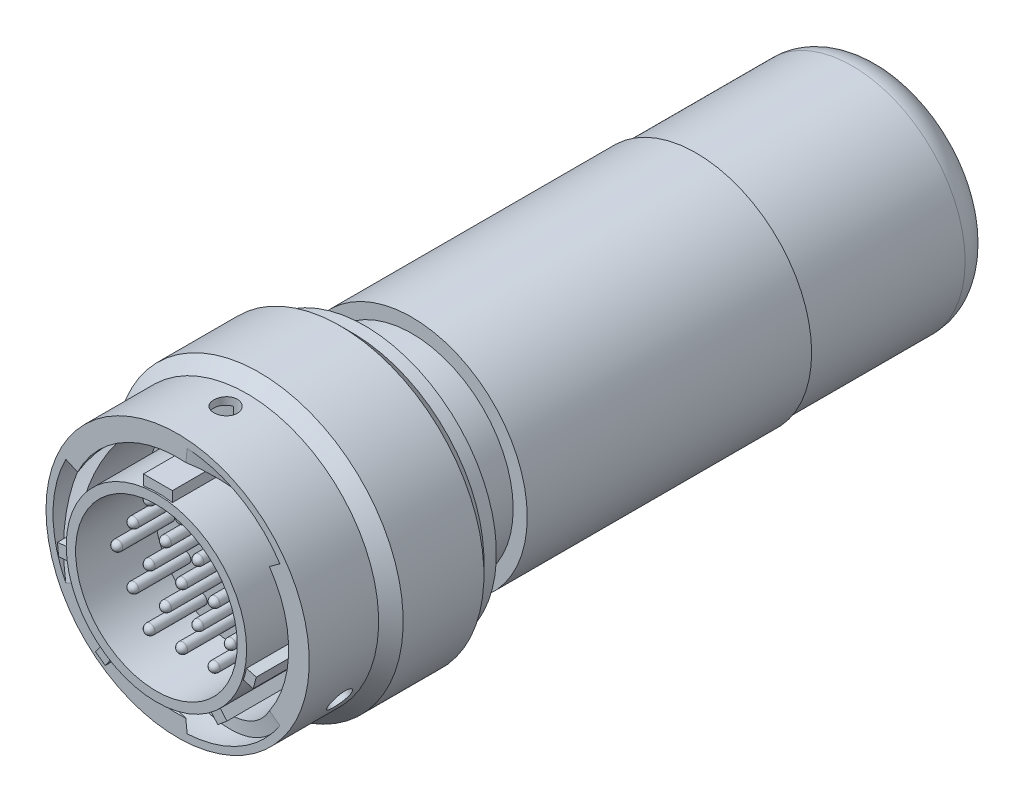
SolidWorks part; units mm, degrees
ref_plane "Front Plane" through (0, 0, 0) normal (0, 0, 1) x (1, 0, 0)
ref_plane "Top Plane" through (0, 0, 0) normal (0, 1, 0) x (1, 0, 0)
ref_plane "Right Plane" through (0, 0, 0) normal (1, 0, 0) x (0, 0, -1)
sketch "Sketch1" plane through (0, 0, 0) normal (1, 0, 0) x (0, 0, -1)
  line L0 (0, 0) -> (74, 0) construction
  line L1 (0, 14.65) -> (0, -14.65) construction
  line L2 (26, 11.75) -> (26, -11.75) construction
  line L3 (74, 11.5) -> (74, -11.5) construction
  line L4 (0, 11.303) -> (0, -11.303) construction
  line L6 (0, 8.2296) -> (0, -8.2296) construction
  line L7 (0, 9.1821) -> (0, -9.1821) construction
  line L8 (7.9502, 8.1407) -> (7.9502, -8.1407) construction
  line L10 (0, 13.4) -> (0, -13.4) construction
  line L13 (0, 0) -> (7.9502, 0) construction
  line L14 (32.5, 10.3187) -> (32.5, -10.3187) construction
  line L15 (9.2202, 10.2235) -> (9.2202, -10.2235) construction
  line L16 (0, 12.7) -> (0, -12.7) construction
  line L17 (32.5, 10.3187) -> (31.23, 10.3187) construction
  point P12 (0.1524, 0)
  point P14 (7.9502, 0)
  point P21 (2.159, 0)
  point P22 (5.842, 0)
  point P25 (30.722, 0)
  point P29 (26, 0)
  point P30 (23.356, 0)
  point P34 (32.5, 0)
  point P42 (9.2202, 0)
  dimension "D1" = 7.366
sketch "Sketch2" plane through (0, 0, 0) normal (0, 0, 1) x (1, 0, 0)
  circle A0 centre (0, 0) radius 9.1821 construction
  circle A1 centre (0, 0) radius 10.2235 construction
  circle A2 centre (0, 0) radius 14.65 construction
  circle A3 centre (0, 0) radius 12.7 construction
sketch "Sketch3" plane through (0, 0, 0) normal (1, 0, 0) x (0, 0, -1)
  line L0 (0, 0) -> (74, 0) construction
  line L1 (9.7282, 10.2235) -> (9.7282, 9.0488)
  line L2 (0, 9.1821) -> (9.2202, 9.1821)
  line L3 (0, 9.1821) -> (0, 8.2296)
  line L4 (0, 8.2296) -> (32.5, 8.2296)
  line L5 (19.8, 9.0488) -> (21.07, 10.3187)
  line L6 (9.7282, 9.0488) -> (19.8, 9.0488)
  line L7 (7.9502, 8.1407) -> (30.722, 8.1407)
  line L8 (7.9502, 8.1407) -> (7.9502, 0)
  line L9 (7.9502, 0) -> (30.722, 0)
  line L10 (30.722, 8.1407) -> (30.722, 0)
  line L11 (21.07, 10.3187) -> (31.23, 10.3187)
  line L12 (31.23, 10.3187) -> (32.5, 9.0488)
  line L13 (31.23, 10.3187) -> (32.5, 10.3187) construction
  line L14 (32.5, 10.3187) -> (32.5, 9.0488) construction
  line L15 (19.8, 9.0488) -> (19.8, 10.3187) construction
  line L16 (19.8, 10.3187) -> (21.07, 10.3187) construction
  line L26 (32.5, 9.0488) -> (32.5, 8.2296)
  line L31 (9.7282, 10.2235) -> (9.2202, 10.2235)
  line L35 (9.2202, 10.2235) -> (9.2202, 9.1821)
  dimension "D1" = 12.7
  dimension "D2" = 0.508
revolve "Revolve1" add sketch "Sketch3" angle 360 about L0
sketch "Sketch4" plane through (0, 0, 0) normal (0, 0, 1) x (1, 0, 0)
  line L0 (-1.4732, 10.1168) -> (1.4732, 10.1168)
  line L1 (0, 10.1168) -> (0, 0) construction
  line L2 (0, 0) -> (9.8576, -2.6413) construction
  line L3 (0, 0) -> (6.5598, -7.8177) construction
  line L4 (0, 0) -> (-5.8535, -8.3597) construction
  line L5 (0, 0) -> (-10.1665, -0.8895) construction
  line L6 (10.0153, -2.0525) -> (9.6998, -3.2302)
  line L7 (7.0268, -7.4259) -> (6.0929, -8.2096)
  line L8 (-5.3542, -8.7094) -> (-6.3529, -8.01)
  line L9 (-10.1133, -1.4967) -> (-10.2196, -0.2822)
  line L10 (10.0153, -2.0525) -> (9.0074, -1.7824)
  line L11 (9.6998, -3.2302) -> (8.6919, -2.9601)
  line L12 (7.0268, -7.4259) -> (6.3561, -6.6265)
  line L13 (6.0929, -8.2096) -> (5.4221, -7.4102)
  line L14 (-5.3542, -8.7094) -> (-4.7557, -7.8546)
  line L15 (-6.3529, -8.01) -> (-5.7544, -7.1553)
  line L16 (-10.1133, -1.4967) -> (-9.0738, -1.4058)
  line L17 (-10.2196, -0.2822) -> (-9.1801, -0.1912)
  line L18 (-1.4732, 10.1168) -> (-1.4732, 9.0631)
  line L19 (1.4732, 10.1168) -> (1.4732, 9.0631)
  arc A0 (5.4221, -7.4102) -> (6.3561, -6.6265) centre (0, 0) ccw
  arc A1 (8.6919, -2.9601) -> (9.0074, -1.7824) centre (0, 0) ccw
  circle A2 centre (0, 0) radius 9.1821 construction
  circle A3 centre (0, 0) radius 10.2235 construction
  arc A4 (-5.7544, -7.1553) -> (-4.7557, -7.8546) centre (0, 0) ccw
  circle A5 centre (0, 0) radius 10.2235 construction
  arc A6 (-9.1801, -0.1912) -> (-9.0738, -1.4058) centre (0, 0) ccw
  arc A7 (1.4732, 9.0631) -> (-1.4732, 9.0631) centre (0, 0) ccw
  dimension "D1" = 2.9464
  dimension "D2" = 105
  dimension "D3" = 140
  dimension "D4" = 215
  dimension "D5" = 265
  dimension "D6" = 1.2192
extrude "Boss-Extrude1" add sketch "Sketch4" against normal up to vertex (9.2202 mm away) from vertex up to point (0, 0, -9.2202) starting at point (0, 0, -0.1524)
sketch "Sketch5" plane through (0, 0, 0) normal (1, 0, 0) x (0, 0, -1)
  line L0 (32.5, 0) -> (0, 0) construction
  line L1 (2.159, 13.4) -> (2.159, 11.303)
  line L3 (17.399, 11.303) -> (17.399, 12.573)
  line L4 (17.399, 12.573) -> (21.209, 12.573)
  line L5 (21.209, 12.573) -> (21.209, 13.4)
  line L6 (2.159, 11.303) -> (17.399, 11.303)
  line L7 (2.159, 13.4) -> (9.2202, 13.4)
  line L8 (21.209, 13.4) -> (19.939, 13.4)
  line L9 (19.939, 13.4) -> (18.689, 14.65)
  line L10 (18.689, 14.65) -> (10.4702, 14.65)
  line L11 (10.4702, 14.65) -> (9.2202, 13.4)
  dimension "D2" = 1.27
  dimension "D5" = 45
  dimension "D1" = 3.81
  dimension "D3" = 19.05
  dimension "D4" = 45
  dimension "D6" = 1.27
revolve "Revolve2" add sketch "Sketch5" angle 360 about L0
sketch "Sketch6" plane through (0, 0, 0) normal (0, 1, 0) x (1, 0, 0)
  line L0 (0, 0) -> (0, 74) construction
  circle A0 centre (0, 7.0358) radius 1.1938
  dimension "D1" = 2.3876
extrude "Cut-Extrude1" cut sketch "Sketch6" along normal through all
sketch "Sketch7" plane through (0, 0, -2.159) normal (0, 0, 1) x (1, 0, 0)
  circle A0 centre (0, 0) radius 11.303 construction
  circle A1 centre (0, 0) radius 11.303
  point P3 (-11.303, 0)
curve "Helix/Spiral1" pitch 19.5072 height 4.8768 radius 11.303 centre (0, 0, -2.159) axis (0, 0, -1) start towards (1, 0, 0)
ref_plane "Plane2" through (-11.303, 0, -2.159) normal (0, 0.9643, -0.2649) x (-1, 0, 0)
sketch "Sketch8" plane through (-11.303, 0, -2.159) normal (0, 0.9643, -0.2649) x (-1, 0, 0)
  line L0 (-11.303, 0) -> (0, 0) construction
  line L1 (0, 0) -> (1.3831, 0) construction
  line L2 (-0.0805, 1.3462) -> (1.3115, 1.3462)
  line L3 (1.3831, 0) -> (1.3831, 2.239) construction
  line L4 (-0.0805, -1.3462) -> (1.3115, -1.3462)
  arc A0 (1.3115, -1.3462) -> (1.3115, 1.3462) centre (-11.303, 0) ccw
  arc A1 (-0.0805, -1.3462) -> (-0.0805, 1.3462) centre (-11.303, 0) ccw
  dimension "GG" = 2.6924
sweep "Cut-Sweep1" cut profiles "Sketch8" path "Helix/Spiral1" align with end faces yes
pattern_circular "CirPattern1" count 3 over 360 about axis through (0, 0, -32.5) along (0, 0, -1) of "Cut-Extrude1", "Cut-Sweep1"
sketch "Sketch9" plane through (0, 0, 0) normal (1, 0, 0) x (0, 0, -1)
  line L0 (26, 11.75) -> (26, 10.3187)
  line L1 (26, 10.3187) -> (70.825, 10.3187)
  line L2 (26, 11.75) -> (54.95, 11.75)
  line L3 (54.95, 11.5) -> (54.95, 11.75)
  line L4 (0, 0) -> (74, 0) construction
  line L5 (54.95, 11.5) -> (70.825, 11.5)
  line L6 (74, 5.15) -> (72.8188, 5.15)
  line L7 (72.8188, 5.15) -> (72.8188, 8.325)
  line L9 (74, 5.15) -> (74, 8.325)
  arc A0 (70.825, 11.5) -> (74, 8.325) centre (70.825, 8.325) cw
  arc A1 (72.8188, 8.325) -> (70.825, 10.3187) centre (70.825, 8.325) ccw
  point P11 (74, 11.5)
  dimension "D1" = 3.175
  dimension "D2" = 19.05
  dimension "D3" = 6.35
revolve "Revolve3" add sketch "Sketch9" angle 360 about L4
sketch "Sketch14-xP" [suppressed] plane through (0, 0, -7.9502) normal (0, 0, 1) x (1, 0, 0)
  line L0 (2.0882, 5.7373) -> (0, 0) construction
  line L1 (0, -6.1055) -> (0, 6.1055) construction
  line L2 (0, 0) -> (5.2875, 3.0528) construction
  line L3 (0, 0) -> (6.0128, -1.0602) construction
  line L4 (0, 0) -> (3.9246, -4.6771) construction
  line L5 (-2.0352, 0) -> (-4.0704, 0) construction
  line L6 (-4.0704, 0) -> (-6.1055, 0) construction
  line L7 (-6.1055, 0) -> (-8.1407, 0) construction
  line L8 (-2.0882, 5.7373) -> (0, 0) construction
  line L9 (0, 0) -> (-5.2875, 3.0528) construction
  line L10 (0, 0) -> (-6.0128, -1.0602) construction
  line L11 (0, 0) -> (-3.9246, -4.6771) construction
  line L12 (1.0176, 1.7625) -> (0, 0) construction
  line L13 (0, 0) -> (1.0176, -1.7625) construction
  line L14 (-2.0352, 0) -> (0, 0) construction
  circle A0 centre (2.0882, 5.7373) radius 0.7938
  circle A1 centre (5.2875, 3.0528) radius 0.7938
  circle A2 centre (6.0128, -1.0602) radius 0.7938
  circle A3 centre (3.9246, -4.6771) radius 0.7938
  circle A4 centre (0, -6.1055) radius 0.7938
  circle A5 centre (-3.9246, -4.6771) radius 0.7938
  circle A6 centre (-6.0128, -1.0602) radius 0.7938
  circle A7 centre (-5.2875, 3.0528) radius 0.7938
  circle A8 centre (-2.0882, 5.7373) radius 0.7938
  circle A9 centre (1.0176, 1.7625) radius 0.7938
  circle A10 centre (1.0176, -1.7625) radius 0.7938
  circle A11 centre (-2.0352, 0) radius 0.7938
  circle A12 centre (0, 0) radius 6.1055 construction
  circle A13 centre (0, 0) radius 2.0352 construction
  circle A15 centre (0, 0) radius 8.1407 construction
  dimension "D1" = 1.5875
  dimension "D2" = 20
  dimension "D3" = 40
  dimension "D4" = 40
  dimension "D5" = 40
  dimension "D6" = 120
  dimension "D7" = 120
extrude "Boss-Extrude14-xP" [suppressed] add sketch "Sketch14-xP" along normal up to vertex up to point (0, 0, -2.159)
fillet "Fillet14-xP" [suppressed] radius 0.7937
sketch "Sketch14-19P" plane through (0, 0, -7.9502) normal (0, 0, 1) x (1, 0, 0)
  line L0 (-3.302, 5.715) -> (3.302, 5.715) construction
  line L1 (0, 5.715) -> (0, -5.715) construction
  line L2 (3.302, 5.715) -> (3.302, -5.715) construction
  line L3 (3.302, -5.715) -> (-3.302, -5.715) construction
  line L4 (-3.302, -5.715) -> (-3.302, 5.715) construction
  line L5 (4.953, 2.8702) -> (4.953, -2.8702) construction
  line L6 (4.953, -2.8702) -> (-4.953, -2.8702) construction
  line L7 (-4.953, -2.8702) -> (-4.953, 2.8702) construction
  line L8 (-4.953, 2.8702) -> (4.953, 2.8702) construction
  line L9 (6.604, 0) -> (-6.604, 0) construction
  line L10 (0, 2.8702) -> (0, -2.8702) construction
  line L11 (-1.651, 2.8702) -> (1.651, 2.8702) construction
  line L12 (1.651, 2.8702) -> (1.651, -2.8702) construction
  line L13 (1.651, -2.8702) -> (-1.651, -2.8702) construction
  line L14 (-1.651, -2.8702) -> (-1.651, 2.8702) construction
  circle A0 centre (0, 5.715) radius 0.508
  circle A1 centre (3.302, 5.715) radius 0.508
  circle A2 centre (4.953, 2.8702) radius 0.508
  circle A3 centre (6.604, 0) radius 0.508
  circle A4 centre (4.953, -2.8702) radius 0.508
  circle A5 centre (3.302, -5.715) radius 0.508
  circle A6 centre (0, -5.715) radius 0.508
  circle A7 centre (-3.302, -5.715) radius 0.508
  circle A8 centre (-4.953, -2.8702) radius 0.508
  circle A9 centre (-6.604, 0) radius 0.508
  circle A10 centre (-4.953, 2.8702) radius 0.508
  circle A11 centre (-3.302, 5.715) radius 0.508
  circle A12 centre (-1.651, 2.8702) radius 0.508
  circle A13 centre (1.651, 2.8702) radius 0.508
  circle A14 centre (3.302, 0) radius 0.508
  circle A15 centre (1.651, -2.8702) radius 0.508
  circle A16 centre (-1.651, -2.8702) radius 0.508
  circle A17 centre (-3.302, 0) radius 0.508
  circle A18 centre (0, 0) radius 0.508
  dimension "D1" = 1.016
  dimension "D2" = 5.715
  dimension "D3" = 3.302
  dimension "D4" = 4.953
  dimension "D5" = 2.8702
  dimension "D6" = 6.604
  dimension "D7" = 1.651
extrude "Boss-Extrude14-19P" add sketch "Sketch14-19P" along normal up to vertex (5.7912 mm away) up to point (0, 0, -2.159)
fillet "Fillet14-19P" radius 0.508 19 edges at (0.508, 5.715, -2.159) (0.508, 0, -2.159) (-1.143, 2.8702, -2.159) (-2.794, 0, -2.159) (-1.143, -2.8702, -2.159) (2.159, -2.8702, -2.159) (3.81, 0, -2.159) (2.159, 2.8702, -2.159) (-2.794, 5.715, -2.159) (-4.445, 2.8702, -2.159) (-6.096, 0, -2.159) (-4.445, -2.8702, -2.159) (-2.794, -5.715, -2.159) (0.508, -5.715, -2.159) (3.81, -5.715, -2.159) (5.461, -2.8702, -2.159) (7.112, 0, -2.159) (5.461, 2.8702, -2.159) (3.81, 5.715, -2.159)
equation "\"D3@Helix/Spiral1\" = \"N@Sketch1\" - \"D@Sketch1\" - \"E@Sketch1\" + ( \"D1@Sketch6\" / 2 ) "
equation "\"D1@Fillet14-xP\" = \"D1@Sketch14-xP\" / 2"
equation "\"D1@Fillet14-19P\" = \"D1@Sketch14-19P\" / 2"
